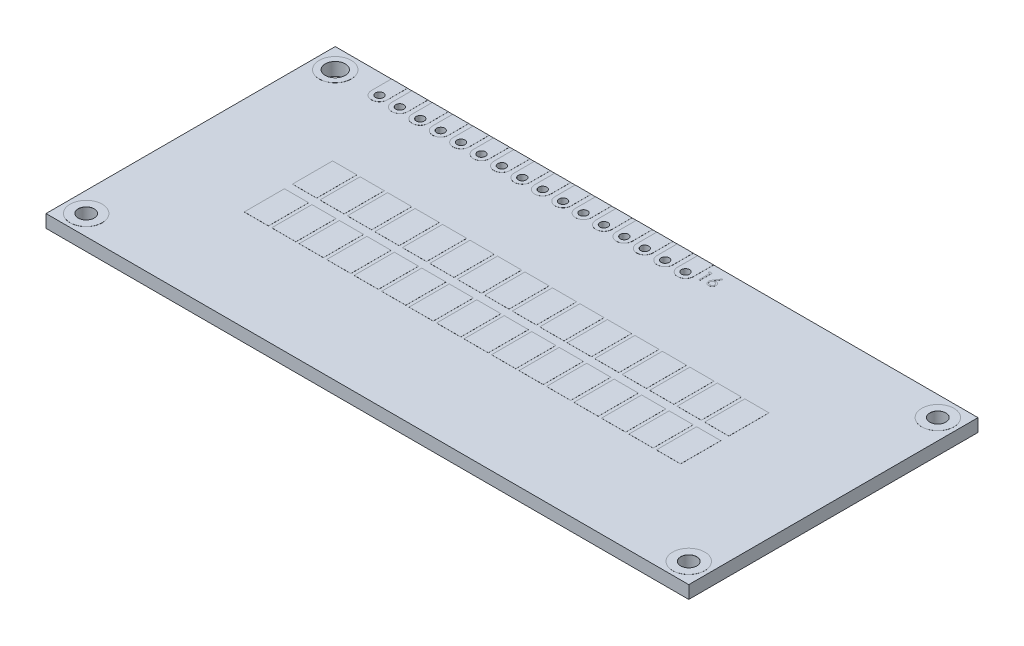
SolidWorks part; units mm, degrees
ref_plane "Alzado" through (0, 0, 0) normal (0, 0, 1) x (1, 0, 0)
ref_plane "Planta" through (0, 0, 0) normal (0, 1, 0) x (1, 0, 0)
ref_plane "Vista lateral" through (0, 0, 0) normal (1, 0, 0) x (0, 0, -1)
sketch "Croquis1" plane through (0, 0, 0) normal (0, 1, 0) x (1, 0, 0)
  line L1 (-40, -18) -> (40, -18)
  line L2 (-40, -18) -> (-40, 18)
  line L3 (-40, 18) -> (40, 18)
  line L4 (40, -18) -> (40, 18)
  line L5 (-40, -18) -> (40, 18) construction
  line L6 (-40, 18) -> (40, -18) construction
  circle A0 centre (-37.5, 15.5) radius 1.25
  circle A1 centre (-37.5, -15.5) radius 1.25
  circle A2 centre (37.5, -15.5) radius 1.25
  circle A3 centre (37.5, 15.5) radius 1.25
  circle A4 centre (-32, 15.5) radius 0.5
  circle A5 centre (-29.46, 15.5) radius 0.5
  circle A6 centre (-26.92, 15.5) radius 0.5
  circle A7 centre (-24.38, 15.5) radius 0.5
  circle A8 centre (-21.84, 15.5) radius 0.5
  circle A9 centre (-19.3, 15.5) radius 0.5
  circle A10 centre (-16.76, 15.5) radius 0.5
  circle A11 centre (-14.22, 15.5) radius 0.5
  circle A12 centre (-11.68, 15.5) radius 0.5
  circle A13 centre (-9.14, 15.5) radius 0.5
  circle A14 centre (-6.6, 15.5) radius 0.5
  circle A15 centre (-4.06, 15.5) radius 0.5
  circle A16 centre (-1.52, 15.5) radius 0.5
  circle A17 centre (1.02, 15.5) radius 0.5
  circle A18 centre (3.56, 15.5) radius 0.5
  circle A19 centre (6.1, 15.5) radius 0.5
  point P0 (0, 0)
  dimension "D3" = 2.5
  dimension "D4" = 2.5
  dimension "D5" = 2.5
  dimension "D8" = 1
  dimension "D10" = 8
  dimension "D1" = 80
  dimension "D2" = 36
  dimension "D6" = 75
  dimension "D7" = 31
  dimension "D9" = 2.5
  dimension "D11" = 16
extrude "Saliente-Extruir1" add sketch "Croquis1" along normal blind 1.6
sketch "Croquis2" plane through (0, 1.6, 0) normal (0, 1, 0) x (1, 0, 0)
  line L0 (-33, 18) -> (-33, 15.5)
  line L1 (40, 18) -> (-40, 18) construction
  line L2 (-31, 15.5) -> (-31, 18)
  line L3 (-31, 18) -> (-33, 18)
  line L4 (-28.46, 18) -> (-30.46, 18)
  line L5 (-28.46, 15.5) -> (-28.46, 18)
  line L6 (-30.46, 18) -> (-30.46, 15.5)
  line L7 (-25.92, 18) -> (-27.92, 18)
  line L8 (-25.92, 15.5) -> (-25.92, 18)
  line L9 (-27.92, 18) -> (-27.92, 15.5)
  line L10 (-23.38, 18) -> (-25.38, 18)
  line L11 (-23.38, 15.5) -> (-23.38, 18)
  line L12 (-25.38, 18) -> (-25.38, 15.5)
  line L13 (-20.84, 18) -> (-22.84, 18)
  line L14 (-20.84, 15.5) -> (-20.84, 18)
  line L15 (-22.84, 18) -> (-22.84, 15.5)
  line L16 (-18.3, 18) -> (-20.3, 18)
  line L17 (-18.3, 15.5) -> (-18.3, 18)
  line L18 (-20.3, 18) -> (-20.3, 15.5)
  line L19 (-15.76, 18) -> (-17.76, 18)
  line L20 (-15.76, 15.5) -> (-15.76, 18)
  line L21 (-17.76, 18) -> (-17.76, 15.5)
  line L22 (-13.22, 18) -> (-15.22, 18)
  line L23 (-13.22, 15.5) -> (-13.22, 18)
  line L24 (-15.22, 18) -> (-15.22, 15.5)
  line L25 (-10.68, 18) -> (-12.68, 18)
  line L26 (-10.68, 15.5) -> (-10.68, 18)
  line L27 (-12.68, 18) -> (-12.68, 15.5)
  line L28 (-8.14, 18) -> (-10.14, 18)
  line L29 (-8.14, 15.5) -> (-8.14, 18)
  line L30 (-10.14, 18) -> (-10.14, 15.5)
  line L31 (-5.6, 18) -> (-7.6, 18)
  line L32 (-5.6, 15.5) -> (-5.6, 18)
  line L33 (-7.6, 18) -> (-7.6, 15.5)
  line L34 (-3.06, 18) -> (-5.06, 18)
  line L35 (-3.06, 15.5) -> (-3.06, 18)
  line L36 (-5.06, 18) -> (-5.06, 15.5)
  line L37 (-0.52, 18) -> (-2.52, 18)
  line L38 (-0.52, 15.5) -> (-0.52, 18)
  line L39 (-2.52, 18) -> (-2.52, 15.5)
  line L40 (2.02, 18) -> (0.02, 18)
  line L41 (2.02, 15.5) -> (2.02, 18)
  line L42 (0.02, 18) -> (0.02, 15.5)
  line L43 (4.56, 18) -> (2.56, 18)
  line L44 (4.56, 15.5) -> (4.56, 18)
  line L45 (2.56, 18) -> (2.56, 15.5)
  line L46 (7.1, 18) -> (5.1, 18)
  line L47 (7.1, 15.5) -> (7.1, 18)
  line L48 (5.1, 18) -> (5.1, 15.5)
  line L49 (-40, 18) -> (-40, -18) construction
  line L50 (-21.395, 5.5) -> (-21.395, 0.5)
  line L51 (-27.825, 5.5) -> (-24.815, 5.5)
  line L52 (-27.825, 5.5) -> (-27.825, 0.5)
  line L53 (-27.825, 0.5) -> (-24.815, 0.5)
  line L54 (-24.815, 5.5) -> (-24.815, 0.5)
  line L55 (-27.825, 5.5) -> (-24.815, 0.5) construction
  line L56 (-27.825, 0.5) -> (-24.815, 5.5) construction
  line L57 (-24.405, 5.5) -> (-21.395, 5.5)
  line L58 (-24.405, 5.5) -> (-24.405, 0.5)
  line L59 (-24.405, 0.5) -> (-21.395, 0.5)
  line L60 (-17.975, 5.5) -> (-17.975, 0.5)
  line L61 (-20.985, 5.5) -> (-17.975, 5.5)
  line L62 (-20.985, 5.5) -> (-20.985, 0.5)
  line L63 (-20.985, 0.5) -> (-17.975, 0.5)
  line L64 (-14.555, 5.5) -> (-14.555, 0.5)
  line L65 (-17.565, 5.5) -> (-14.555, 5.5)
  line L66 (-17.565, 5.5) -> (-17.565, 0.5)
  line L67 (-17.565, 0.5) -> (-14.555, 0.5)
  line L68 (-11.135, 5.5) -> (-11.135, 0.5)
  line L69 (-14.145, 5.5) -> (-11.135, 5.5)
  line L70 (-14.145, 5.5) -> (-14.145, 0.5)
  line L71 (-14.145, 0.5) -> (-11.135, 0.5)
  line L72 (-7.715, 5.5) -> (-7.715, 0.5)
  line L73 (-10.725, 5.5) -> (-7.715, 5.5)
  line L74 (-10.725, 5.5) -> (-10.725, 0.5)
  line L75 (-10.725, 0.5) -> (-7.715, 0.5)
  line L76 (-4.295, 5.5) -> (-4.295, 0.5)
  line L77 (-7.305, 5.5) -> (-4.295, 5.5)
  line L78 (-7.305, 5.5) -> (-7.305, 0.5)
  line L79 (-7.305, 0.5) -> (-4.295, 0.5)
  line L80 (-0.875, 5.5) -> (-0.875, 0.5)
  line L81 (-3.885, 5.5) -> (-0.875, 5.5)
  line L82 (-3.885, 5.5) -> (-3.885, 0.5)
  line L83 (-3.885, 0.5) -> (-0.875, 0.5)
  line L84 (2.545, 5.5) -> (2.545, 0.5)
  line L85 (-0.465, 5.5) -> (2.545, 5.5)
  line L86 (-0.465, 5.5) -> (-0.465, 0.5)
  line L87 (-0.465, 0.5) -> (2.545, 0.5)
  line L88 (5.965, 5.5) -> (5.965, 0.5)
  line L89 (2.955, 5.5) -> (5.965, 5.5)
  line L90 (2.955, 5.5) -> (2.955, 0.5)
  line L91 (2.955, 0.5) -> (5.965, 0.5)
  line L92 (9.385, 5.5) -> (9.385, 0.5)
  line L93 (6.375, 5.5) -> (9.385, 5.5)
  line L94 (6.375, 5.5) -> (6.375, 0.5)
  line L95 (6.375, 0.5) -> (9.385, 0.5)
  line L96 (12.805, 5.5) -> (12.805, 0.5)
  line L97 (9.795, 5.5) -> (12.805, 5.5)
  line L98 (9.795, 5.5) -> (9.795, 0.5)
  line L99 (9.795, 0.5) -> (12.805, 0.5)
  line L100 (16.225, 5.5) -> (16.225, 0.5)
  line L101 (13.215, 5.5) -> (16.225, 5.5)
  line L102 (13.215, 5.5) -> (13.215, 0.5)
  line L103 (13.215, 0.5) -> (16.225, 0.5)
  line L104 (19.645, 5.5) -> (19.645, 0.5)
  line L105 (16.635, 5.5) -> (19.645, 5.5)
  line L106 (16.635, 5.5) -> (16.635, 0.5)
  line L107 (16.635, 0.5) -> (19.645, 0.5)
  line L108 (23.065, 5.5) -> (23.065, 0.5)
  line L109 (20.055, 5.5) -> (23.065, 5.5)
  line L110 (20.055, 5.5) -> (20.055, 0.5)
  line L111 (20.055, 0.5) -> (23.065, 0.5)
  line L112 (26.485, 5.5) -> (26.485, 0.5)
  line L113 (23.475, 5.5) -> (26.485, 5.5)
  line L114 (23.475, 5.5) -> (23.475, 0.5)
  line L115 (23.475, 0.5) -> (26.485, 0.5)
  line L116 (-40, -18) -> (40, -18) construction
  line L117 (-27.825, -0.5) -> (-24.815, -0.5)
  line L118 (-27.825, -0.5) -> (-27.825, -5.5)
  line L119 (-27.825, -5.5) -> (-24.815, -5.5)
  line L120 (-24.815, -0.5) -> (-24.815, -5.5)
  line L121 (-27.825, -0.5) -> (-24.815, -5.5) construction
  line L122 (-27.825, -5.5) -> (-24.815, -0.5) construction
  line L123 (-24.405, -0.5) -> (-21.395, -0.5)
  line L124 (-21.395, -0.5) -> (-21.395, -5.5)
  line L125 (-24.405, -5.5) -> (-21.395, -5.5)
  line L126 (-24.405, -0.5) -> (-24.405, -5.5)
  line L127 (-20.985, -0.5) -> (-17.975, -0.5)
  line L128 (-17.975, -0.5) -> (-17.975, -5.5)
  line L129 (-20.985, -5.5) -> (-17.975, -5.5)
  line L130 (-20.985, -0.5) -> (-20.985, -5.5)
  line L131 (-17.565, -0.5) -> (-14.555, -0.5)
  line L132 (-14.555, -0.5) -> (-14.555, -5.5)
  line L133 (-17.565, -5.5) -> (-14.555, -5.5)
  line L134 (-17.565, -0.5) -> (-17.565, -5.5)
  line L135 (-14.145, -0.5) -> (-11.135, -0.5)
  line L136 (-11.135, -0.5) -> (-11.135, -5.5)
  line L137 (-14.145, -5.5) -> (-11.135, -5.5)
  line L138 (-14.145, -0.5) -> (-14.145, -5.5)
  line L139 (-10.725, -0.5) -> (-7.715, -0.5)
  line L140 (-7.715, -0.5) -> (-7.715, -5.5)
  line L141 (-10.725, -5.5) -> (-7.715, -5.5)
  line L142 (-10.725, -0.5) -> (-10.725, -5.5)
  line L143 (-7.305, -0.5) -> (-4.295, -0.5)
  line L144 (-4.295, -0.5) -> (-4.295, -5.5)
  line L145 (-7.305, -5.5) -> (-4.295, -5.5)
  line L146 (-7.305, -0.5) -> (-7.305, -5.5)
  line L147 (-3.885, -0.5) -> (-0.875, -0.5)
  line L148 (-0.875, -0.5) -> (-0.875, -5.5)
  line L149 (-3.885, -5.5) -> (-0.875, -5.5)
  line L150 (-3.885, -0.5) -> (-3.885, -5.5)
  line L151 (-0.465, -0.5) -> (2.545, -0.5)
  line L152 (2.545, -0.5) -> (2.545, -5.5)
  line L153 (-0.465, -5.5) -> (2.545, -5.5)
  line L154 (-0.465, -0.5) -> (-0.465, -5.5)
  line L155 (2.955, -0.5) -> (5.965, -0.5)
  line L156 (5.965, -0.5) -> (5.965, -5.5)
  line L157 (2.955, -5.5) -> (5.965, -5.5)
  line L158 (2.955, -0.5) -> (2.955, -5.5)
  line L159 (6.375, -0.5) -> (9.385, -0.5)
  line L160 (9.385, -0.5) -> (9.385, -5.5)
  line L161 (6.375, -5.5) -> (9.385, -5.5)
  line L162 (6.375, -0.5) -> (6.375, -5.5)
  line L163 (9.795, -0.5) -> (12.805, -0.5)
  line L164 (12.805, -0.5) -> (12.805, -5.5)
  line L165 (9.795, -5.5) -> (12.805, -5.5)
  line L166 (9.795, -0.5) -> (9.795, -5.5)
  line L167 (13.215, -0.5) -> (16.225, -0.5)
  line L168 (16.225, -0.5) -> (16.225, -5.5)
  line L169 (13.215, -5.5) -> (16.225, -5.5)
  line L170 (13.215, -0.5) -> (13.215, -5.5)
  line L171 (16.635, -0.5) -> (19.645, -0.5)
  line L172 (19.645, -0.5) -> (19.645, -5.5)
  line L173 (16.635, -5.5) -> (19.645, -5.5)
  line L174 (16.635, -0.5) -> (16.635, -5.5)
  line L175 (20.055, -0.5) -> (23.065, -0.5)
  line L176 (23.065, -0.5) -> (23.065, -5.5)
  line L177 (20.055, -5.5) -> (23.065, -5.5)
  line L178 (20.055, -0.5) -> (20.055, -5.5)
  line L179 (23.475, -0.5) -> (26.485, -0.5)
  line L180 (26.485, -0.5) -> (26.485, -5.5)
  line L181 (23.475, -5.5) -> (26.485, -5.5)
  line L182 (23.475, -0.5) -> (23.475, -5.5)
  arc A0 (-33, 15.5) -> (-31, 15.5) centre (-32, 15.5) ccw
  circle A1 centre (-32, 15.5) radius 0.5 construction
  arc A2 (-30.46, 15.5) -> (-28.46, 15.5) centre (-29.46, 15.5) ccw
  arc A3 (-27.92, 15.5) -> (-25.92, 15.5) centre (-26.92, 15.5) ccw
  arc A4 (-25.38, 15.5) -> (-23.38, 15.5) centre (-24.38, 15.5) ccw
  arc A5 (-22.84, 15.5) -> (-20.84, 15.5) centre (-21.84, 15.5) ccw
  arc A6 (-20.3, 15.5) -> (-18.3, 15.5) centre (-19.3, 15.5) ccw
  arc A7 (-17.76, 15.5) -> (-15.76, 15.5) centre (-16.76, 15.5) ccw
  arc A8 (-15.22, 15.5) -> (-13.22, 15.5) centre (-14.22, 15.5) ccw
  arc A9 (-12.68, 15.5) -> (-10.68, 15.5) centre (-11.68, 15.5) ccw
  arc A10 (-10.14, 15.5) -> (-8.14, 15.5) centre (-9.14, 15.5) ccw
  arc A11 (-7.6, 15.5) -> (-5.6, 15.5) centre (-6.6, 15.5) ccw
  arc A12 (-5.06, 15.5) -> (-3.06, 15.5) centre (-4.06, 15.5) ccw
  arc A13 (-2.52, 15.5) -> (-0.52, 15.5) centre (-1.52, 15.5) ccw
  arc A14 (0.02, 15.5) -> (2.02, 15.5) centre (1.02, 15.5) ccw
  arc A15 (2.56, 15.5) -> (4.56, 15.5) centre (3.56, 15.5) ccw
  arc A16 (5.1, 15.5) -> (7.1, 15.5) centre (6.1, 15.5) ccw
  circle A17 centre (-37.5, 15.5) radius 2
  circle A18 centre (37.5, -15.5) radius 1
  circle A19 centre (-37.5, -15.5) radius 2
  circle A20 centre (37.5, -15.5) radius 2
  circle A21 centre (37.5, 15.5) radius 2
  circle A22 centre (37.5, 15.5) radius 1
  circle A23 centre (-37.5, -15.5) radius 1
  circle A24 centre (-37.5, 15.5) radius 1.25
  circle A25 centre (-32, 15.5) radius 0.5
  circle A26 centre (-29.46, 15.5) radius 0.5
  circle A27 centre (-26.92, 15.5) radius 0.5
  circle A28 centre (-24.38, 15.5) radius 0.5
  circle A29 centre (-21.84, 15.5) radius 0.5
  circle A30 centre (-19.3, 15.5) radius 0.5
  circle A31 centre (-16.76, 15.5) radius 0.5
  circle A32 centre (-14.22, 15.5) radius 0.5
  circle A33 centre (-11.68, 15.5) radius 0.5
  circle A34 centre (-9.14, 15.5) radius 0.5
  circle A35 centre (-6.6, 15.5) radius 0.5
  circle A36 centre (-4.06, 15.5) radius 0.5
  circle A37 centre (-1.52, 15.5) radius 0.5
  circle A38 centre (1.02, 15.5) radius 0.5
  circle A39 centre (3.56, 15.5) radius 0.5
  circle A40 centre (6.1, 15.5) radius 0.5
  circle A41 centre (-37.5, 15.5) radius 1.25 construction
  point P86 (-26.32, -3)
  point P97 (-26.32, 3)
  dimension "D3" = 4
  dimension "D1" = 2
  dimension "D4" = 3.01
  dimension "D5" = 5
  dimension "D6" = 12.175
  dimension "D7" = 12.5
  dimension "D9" = 5
  dimension "D10" = 12.5
  dimension "D2" = 16
  dimension "D8" = 16
  dimension "D11" = 16
  dimension "D12" = 16
extrude "Saliente-Extruir3" add sketch "Croquis2" along normal blind 0.01
sketch "Croquis3" plane through (0, 1.6, 0) normal (0, 1, 0) x (1, 0, 0)
  line L1 (-35.35, -11.9) -> (35.35, -11.9)
  line L2 (-35.35, -11.9) -> (-35.35, 11.9)
  line L3 (-35.35, 11.9) -> (35.35, 11.9)
  line L4 (35.35, -11.9) -> (35.35, 11.9)
  line L5 (-35.35, -11.9) -> (35.35, 11.9) construction
  line L6 (-35.35, 11.9) -> (35.35, -11.9) construction
  point P0 (0, 0)
  dimension "D1" = 70.7
  dimension "D2" = 23.8
sketch "Croquis5" plane through (0, 1.6, 0) normal (0, 1, 0) x (1, 0, 0)
  line L0 (6.1, 15.5) -> (10.675, 15.5) construction
  text T0 "  16" font "Century Gothic" height 1.5
extrude "Saliente-Extruir5" add sketch "Croquis5" along normal blind 0.01
sketch "Croquis6" plane through (0, 0, 0) normal (0, -1, 0) x (1, 0, 0)
  circle A0 centre (0, 0) radius 7.5
  dimension "D1" = 15
extrude "Saliente-Extruir6" add sketch "Croquis6" along normal blind 2
fillet "Redondeo1" radius 15 1 edges at (0, -2, -7.5)
